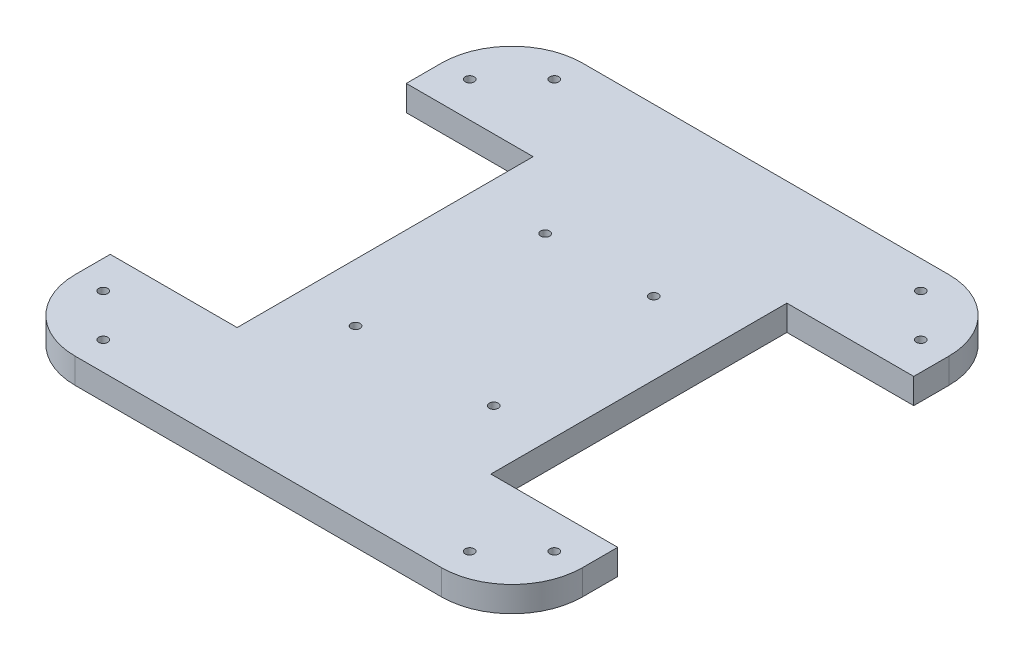
SolidWorks part; units mm, degrees
ref_plane "Front Plane" through (0, 0, 0) normal (0, 0, 1) x (1, 0, 0)
ref_plane "Top Plane" through (0, 0, 0) normal (0, 1, 0) x (1, 0, 0)
ref_plane "Right Plane" through (0, 0, 0) normal (1, 0, 0) x (0, 0, -1)
sketch "Sketch1" plane through (0, 0, 0) normal (0, 1, 0) x (1, 0, 0)
  line L1 (-65, -90) -> (65, -90)
  line L2 (-90, -65) -> (-90, 65)
  line L3 (-65, 90) -> (65, 90)
  line L4 (90, -65) -> (90, 65)
  arc A0 (-90, 65) -> (-65, 90) centre (-65, 65) cw
  arc A1 (65, 90) -> (90, 65) centre (65, 65) cw
  arc A2 (90, -65) -> (65, -90) centre (65, -65) cw
  arc A3 (-65, -90) -> (-90, -65) centre (-65, -65) cw
  point P4 (-90, 0)
  point P6 (0, 90)
  dimension "D3" = 25
  dimension "D1" = 180
  dimension "D2" = 180
extrude "Plate" add sketch "Sketch1" along normal blind 9
sketch "Sketch3" plane through (0, 9, 0) normal (0, 1, 0) x (1, 0, 0)
  line L0 (-65, 90) -> (-65, -90) construction
  line L1 (65, 90) -> (65, -90) construction
  line L2 (-90, 65) -> (90, 65) construction
  line L3 (-90, -65) -> (90, -65) construction
  circle A0 centre (-65, 80) radius 1.6
  circle A1 centre (-80, 65) radius 1.6
  circle A2 centre (80, 65) radius 1.6
  circle A3 centre (80, -65) radius 1.6
  circle A4 centre (65, 80) radius 1.6
  circle A5 centre (65, -80) radius 1.6
  circle A6 centre (-65, -80) radius 1.6
  circle A7 centre (-80, -65) radius 1.6
  dimension "D1" = 3.2
  dimension "D2" = 15
  dimension "D3" = 15
  dimension "D4" = 15
  dimension "D5" = 15
  dimension "D6" = 15
  dimension "D7" = 15
  dimension "D8" = 15
  dimension "D9" = 15
extrude "Hex Holes" cut sketch "Sketch3" against normal through all
sketch "Sketch4" plane through (0, 9, 0) normal (0, 1, 0) x (1, 0, 0)
  line L0 (-90, -65) -> (-90, 65) construction
  line L1 (-65, -90) -> (65, -90) construction
  circle A0 centre (-24.5, -31) radius 1.6
  circle A1 centre (24.5, -31) radius 1.6
  circle A2 centre (-19.25, 31) radius 1.6
  circle A3 centre (19.25, 31) radius 1.6
  dimension "D1" = 3.2
  dimension "D2" = 62
  dimension "D3" = 49
  dimension "D4" = 5.25
  dimension "D5" = 38.5
  dimension "D6" = 65.5
  dimension "D7" = 59
extrude "Arduino Holes" cut sketch "Sketch4" against normal through all
sketch "Sketch5" plane through (0, 9, 0) normal (0, 1, 0) x (1, 0, 0)
  line L0 (-90, 52.5) -> (-45, 52.5)
  line L1 (-90, -65) -> (-90, 65) construction
  line L2 (-45, 52.5) -> (-45, -52.5)
  line L3 (-45, -52.5) -> (-90, -52.5)
  line L4 (-90, 52.5) -> (-90, -52.5)
  line L5 (90, -65) -> (90, 65) construction
  line L6 (90, 52.5) -> (45, 52.5)
  line L7 (90, 52.5) -> (90, -52.5)
  line L8 (90, -52.5) -> (45, -52.5)
  line L9 (45, 52.5) -> (45, -52.5)
  line L10 (-90, 0) -> (90, 0) construction
  point P16 (-90, 0)
  point P17 (90, 0)
  dimension "D1" = 105
  dimension "D2" = 45
extrude "Cut-Extrude1" cut sketch "Sketch5" against normal through all
